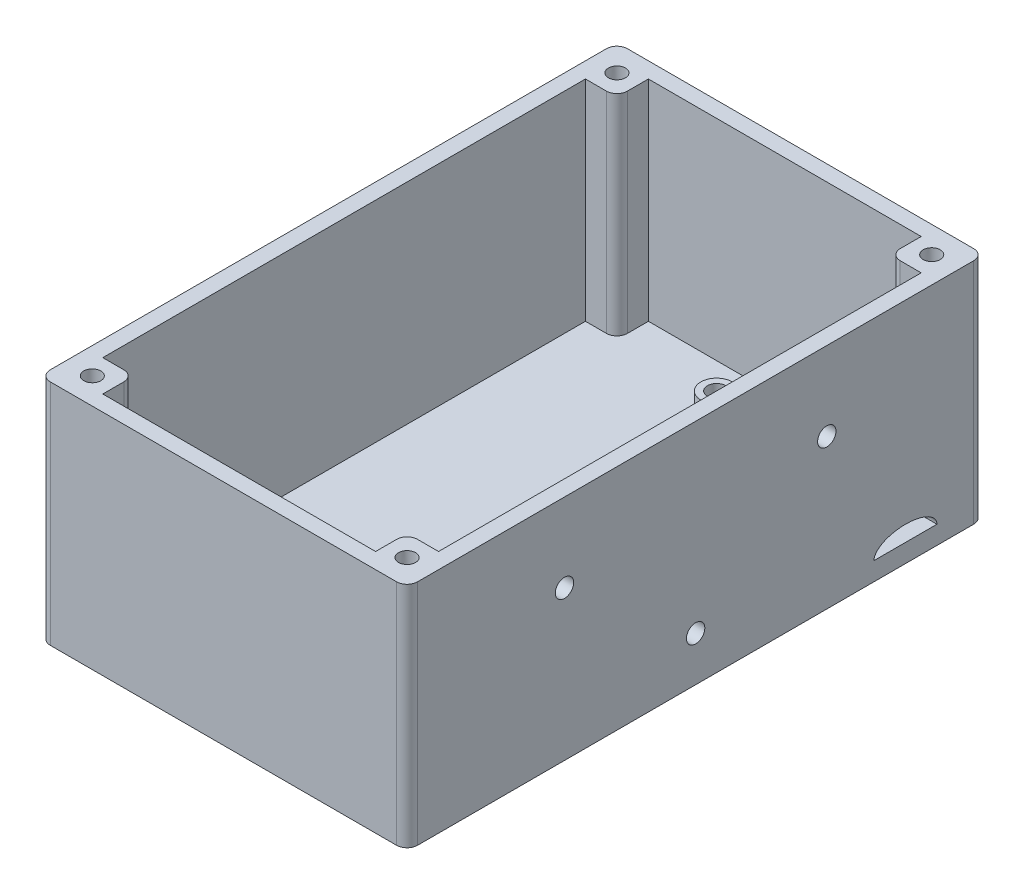
SolidWorks part; units mm, degrees
ref_plane "Front Plane" through (0, 0, 0) normal (0, 0, 1) x (1, 0, 0)
ref_plane "Top Plane" through (0, 0, 0) normal (0, 1, 0) x (1, 0, 0)
ref_plane "Right Plane" through (0, 0, 0) normal (1, 0, 0) x (0, 0, -1)
sketch "Sketch1" plane through (0, 0, 0) normal (0, 1, 0) x (1, 0, 0)
  line L1 (35, -55) -> (-35, -55)
  line L2 (35, -55) -> (35, 55)
  line L3 (35, 55) -> (-35, 55)
  line L4 (-35, -55) -> (-35, 55)
  line L5 (35, -55) -> (-35, 55) construction
  line L6 (35, 55) -> (-35, -55) construction
  point P0 (0, 0)
  dimension "D1" = 110
  dimension "D2" = 70
extrude "Bottom" add sketch "Sketch1" along normal blind 3.5
sketch "Sketch3" plane through (0, 3.5, 0) normal (0, 1, 0) x (1, 0, 0)
  line L0 (-35, 55) -> (35, 55)
  line L1 (35, 55) -> (35, -55)
  line L2 (35, -55) -> (-35, -55)
  line L3 (-35, -55) -> (-35, 55)
  line L4 (-26, 52) -> (-4, 52)
  line L5 (32, 46) -> (32, -46)
  line L6 (26, -52) -> (4, -52)
  line L8 (-32, 46) -> (-26, 46)
  line L9 (-26, 46) -> (-26, 52)
  line L10 (26, 52) -> (26, 46)
  line L11 (26, 46) -> (32, 46)
  line L12 (32, -46) -> (26, -46)
  line L13 (26, -46) -> (26, -52)
  line L14 (-32, -46) -> (-26, -46)
  line L15 (-26, -46) -> (-26, -52)
  line L16 (-32, -46) -> (-32, 46)
  line L23 (-4, 52) -> (26, 52)
  line L26 (4, -52) -> (-26, -52)
  dimension "D1" = 3
  dimension "D2" = 3
  dimension "D3" = 3
  dimension "D4" = 3
  dimension "D5" = 6
extrude "Wall" add sketch "Sketch3" along normal blind 40
sketch "Sketch4" plane through (0, 43.5, 0) normal (0, 1, 0) x (1, 0, 0)
  line L0 (-35, 55) -> (-35, -55) construction
  line L1 (35, 55) -> (-35, 55) construction
  line L2 (35, -55) -> (35, 55) construction
  line L3 (-35, -55) -> (35, -55) construction
  line L5 (35, 0) -> (33.8613, 0) construction
  circle A0 centre (-30, 50) radius 1.625
  circle A1 centre (30, 50) radius 1.625
  circle A2 centre (30, -50) radius 1.625
  circle A3 centre (-30, -50) radius 1.625
  dimension "D1" = 3.25
  dimension "D4" = 5
  dimension "D2" = 5
  dimension "D3" = 5
  dimension "D5" = 5
extrude "Top Plate Screw Holes" cut sketch "Sketch4" against normal blind 30 draft 1
fillet "Fillet1" radius 2 1 edges at (-26, 23.5, 46) type face fillet first side face at (-29, 23.5, 46) second side face at (-26, 23.5, 49)
fillet "Fillet2" radius 2 1 edges at (26, 23.5, 46) type face fillet first side face at (26, 23.5, 49) second side face at (29, 23.5, 46)
fillet "Fillet3" radius 2 1 edges at (26, 23.5, -46) type face fillet first side face at (26, 23.5, -49) second side face at (29, 23.5, -46)
fillet "Fillet4" radius 2 1 edges at (-26, 23.5, -46) type face fillet first side face at (-29, 23.5, -46) second side face at (-26, 23.5, -49)
fillet "Fillet5" radius 2 1 edges at (-35, 21.75, -55) type face fillet first side face at (-35, 21.75, 0) second side face at (0, 21.75, -55)
fillet "Fillet6" radius 2 1 edges at (35, 21.75, -55) type face fillet first side face at (1, 21.75, -55) second side face at (35, 21.75, 0)
fillet "Fillet7" radius 2 1 edges at (35, 21.75, 55) type face fillet first side face at (35, 21.75, 1) second side face at (0, 21.75, 55)
fillet "Fillet8" radius 2 1 edges at (-35, 21.75, 55) type face fillet first side face at (-1, 21.75, 55) second side face at (-35, 21.75, 1)
sketch "M4 Mount" plane through (0, 3.5, 0) normal (0, -1, 0) x (1, 0, 0)
  line L1 (0, 0) -> (23.8675, 0) construction
  line L2 (0, 0) -> (0, -20) construction
  circle A0 centre (0, -20) radius 2.1
  circle A1 centre (0, 20) radius 2.1
  dimension "D1" = 4.2
  dimension "D3" = 20
  dimension "D4" = 20
extrude "M4 Mount Cut" cut sketch "M4 Mount" along normal through all
sketch "M4 Screw Heads" plane through (0, 3.5, 0) normal (0, 1, 0) x (1, 0, 0)
  circle A0 centre (0, -20) radius 3.75
  circle A1 centre (0, 20) radius 3.75
  dimension "D1" = 7.5
extrude "M4 Screw CUT" cut sketch "M4 Screw Heads" against normal blind 10 draft 45
sketch "Sketch5" plane through (32, 0, 0) normal (-1, 0, 0) x (0, 0, 1)
  line L1 (-46, 3.5) -> (-34, 3.5)
  line L2 (46, 3.5) -> (-46, 3.5) construction
  ellipse E0 centre (-40, 3.5) end of major axis (-34, 3.5) minor radius 3 (-34, 3.5) -> (-46, 3.5) ccw
  dimension "D1" = 3
  dimension "D2" = 12
extrude "Cable Pass CUT" cut sketch "Sketch5" against normal blind 10
sketch "Sketch6" plane through (32, 0, 0) normal (-1, 0, 0) x (0, 0, 1)
  line L0 (0, 43.5) -> (0, 18.1138) construction
  line L1 (46, 43.5) -> (-46, 43.5) construction
  line L2 (-46, 23.5) -> (-28.6375, 23.5) construction
  line L3 (-46, 43.5) -> (-46, 3.5) construction
  circle A0 centre (-25, 28.5) radius 1.75
  circle A1 centre (25, 28.5) radius 1.75
  circle A2 centre (0, 8.5) radius 1.75
  dimension "D1" = 3.5
  dimension "D3" = 15
  dimension "D2" = 25
  dimension "D4" = 5
extrude "M3 Connection CUT" cut sketch "Sketch6" against normal blind 10
sketch "Sketch7" plane through (0, 3.5, 0) normal (0, 1, 0) x (1, 0, 0)
  line L0 (32, -46) -> (32, 46) construction
  line L1 (26, 52) -> (-26, 52) construction
  circle A0 centre (12, 42) radius 3
  circle A1 centre (12, 27) radius 3
  circle A2 centre (-3, 42) radius 3
  dimension "D1" = 6
  dimension "D3" = 20
  dimension "D2" = 15
  dimension "D4" = 10
  dimension "D5" = 15
extrude "M3 Board Mount EXT" add sketch "Sketch7" along normal blind 5
sketch "Sketch8" plane through (0, 8.5, 0) normal (0, 1, 0) x (1, 0, 0)
  circle A0 centre (12, 42) radius 1.75
  circle A1 centre (-3, 42) radius 1.75
  circle A2 centre (12, 27) radius 1.75
  dimension "D1" = 3.5
extrude "M3 Board Screw CUT" cut sketch "Sketch8" against normal through all
sketch "Sketch9" plane through (0, 0, 0) normal (0, -1, 0) x (1, 0, 0)
  line L1 (-3, -38.8246) -> (-5.75, -40.4123)
  line L2 (-5.75, -40.4123) -> (-5.75, -43.5877)
  line L3 (-5.75, -43.5877) -> (-3, -45.1754)
  line L4 (-3, -45.1754) -> (-0.25, -43.5877)
  line L5 (-0.25, -43.5877) -> (-0.25, -40.4123)
  line L6 (-0.25, -40.4123) -> (-3, -38.8246)
  line L7 (12, -38.8246) -> (9.25, -40.4123)
  line L8 (9.25, -40.4123) -> (9.25, -43.5877)
  line L9 (9.25, -43.5877) -> (12, -45.1754)
  line L10 (12, -45.1754) -> (14.75, -43.5877)
  line L11 (14.75, -43.5877) -> (14.75, -40.4123)
  line L12 (14.75, -40.4123) -> (12, -38.8246)
  line L13 (12, -23.8246) -> (9.25, -25.4123)
  line L14 (9.25, -25.4123) -> (9.25, -28.5877)
  line L15 (9.25, -28.5877) -> (12, -30.1754)
  line L16 (12, -30.1754) -> (14.75, -28.5877)
  line L17 (14.75, -28.5877) -> (14.75, -25.4123)
  line L18 (14.75, -25.4123) -> (12, -23.8246)
  circle A0 centre (-3, -42) radius 2.75 construction
  circle A1 centre (12, -42) radius 2.75 construction
  circle A2 centre (12, -27) radius 2.75 construction
  dimension "D1" = 5.5
  dimension "D2" = 5.5
  dimension "D3" = 5.5
extrude "M3 Nut Circuit Board CUT" cut sketch "Sketch9" against normal blind 3.5
equation "\"BOXWALL\"=3"
equation "\"D1@Sketch3\"=\"BOXWALL\""
equation "\"D2@Sketch3\"=\"BOXWALL\""
equation "\"D3@Sketch3\"=\"BOXWALL\""
equation "\"D4@Sketch3\"=\"BOXWALL\""
equation "\"SCREW_M3\"=3.5"
equation "\"D1@Sketch6\"=\"SCREW_M3\""
equation "\"D1@Sketch7\"=6mm"
equation "\"D1@Sketch8\"=\"SCREW_M3\""
equation "\"SCREW_M3_NUT\"=5.5"
equation "\"D1@Sketch9\"=\"SCREW_M3_NUT\""
equation "\"D2@Sketch9\"=\"SCREW_M3_NUT\""
equation "\"D3@Sketch9\"=\"SCREW_M3_NUT\""
